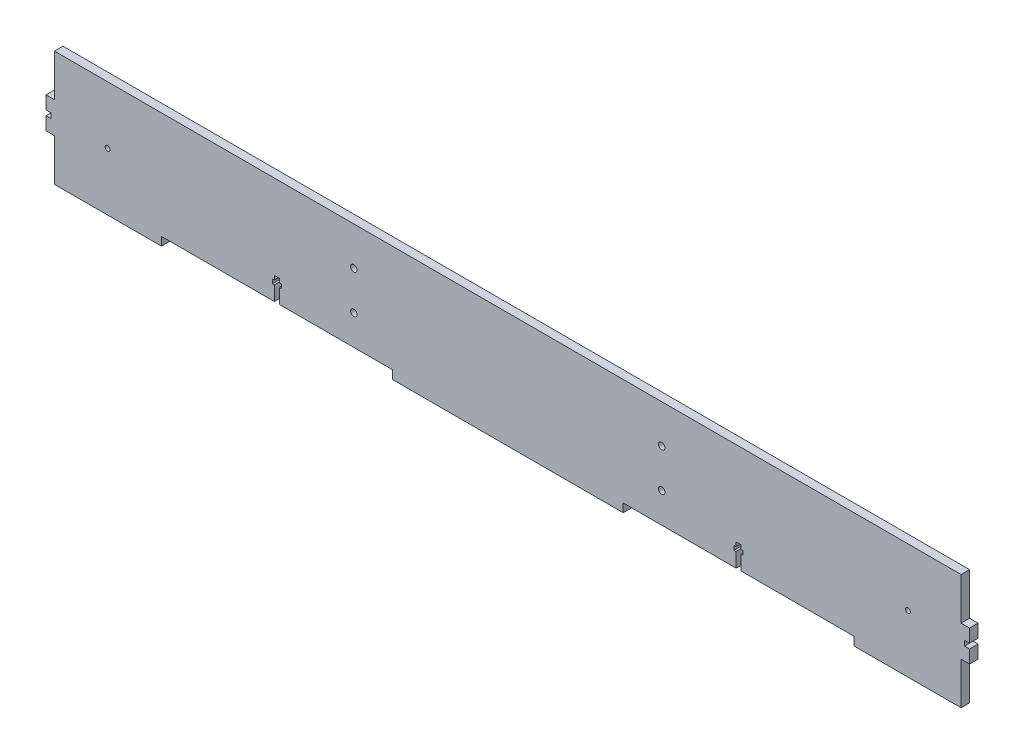
SolidWorks part; units mm, degrees
ref_plane "Front Plane" through (0, 0, 0) normal (0, 0, 1) x (1, 0, 0)
ref_plane "Top Plane" through (0, 0, 0) normal (0, 1, 0) x (1, 0, 0)
ref_plane "Right Plane" through (0, 0, 0) normal (1, 0, 0) x (0, 0, -1)
sketch "Sketch1" plane through (0, 0, 0) normal (0, 0, 1) x (1, 0, 0)
  line L0 (308.5, 78) -> (308.5, 50.625)
  line L1 (308.5, 50.625) -> (303, 50.625)
  line L2 (303, 50.625) -> (303, 42.125)
  line L3 (303, 42.125) -> (306.25, 42.125)
  line L4 (306.25, 42.125) -> (306.25, 40.5)
  line L5 (306.25, 40.5) -> (306.25, 38.875)
  line L6 (306.25, 38.875) -> (303, 38.875)
  line L7 (303, 38.875) -> (303, 30.375)
  line L8 (303, 30.375) -> (308.5, 30.375)
  line L9 (308.5, 30.375) -> (308.5, 3)
  line L10 (308.5, 3) -> (378, 3)
  line L11 (378, 3) -> (378, 8.5)
  line L12 (378, 8.5) -> (451.375, 8.5)
  line L13 (451.375, 8.5) -> (451.375, 17.95)
  line L14 (451.375, 17.95) -> (450.125, 17.95)
  line L15 (450.125, 17.95) -> (450.125, 20.6)
  line L16 (450.125, 20.6) -> (451.375, 20.6)
  line L17 (451.375, 20.6) -> (451.375, 23.25)
  line L18 (451.375, 23.25) -> (454.625, 23.25)
  line L19 (454.625, 23.25) -> (454.625, 20.6)
  line L20 (454.625, 20.6) -> (455.875, 20.6)
  line L21 (455.875, 20.6) -> (455.875, 17.95)
  line L22 (455.875, 17.95) -> (454.625, 17.95)
  line L23 (454.625, 17.95) -> (454.625, 8.5)
  line L24 (454.625, 8.5) -> (528, 8.5)
  line L25 (528, 8.5) -> (528, 3)
  line L26 (528, 3) -> (678, 3)
  line L27 (678, 3) -> (678, 8.5)
  line L28 (678, 8.5) -> (751.375, 8.5)
  line L29 (751.375, 8.5) -> (751.375, 17.95)
  line L30 (751.375, 17.95) -> (750.125, 17.95)
  line L31 (750.125, 17.95) -> (750.125, 20.6)
  line L32 (750.125, 20.6) -> (751.375, 20.6)
  line L33 (751.375, 20.6) -> (751.375, 23.25)
  line L34 (751.375, 23.25) -> (754.625, 23.25)
  line L35 (754.625, 23.25) -> (754.625, 20.6)
  line L36 (754.625, 20.6) -> (755.875, 20.6)
  line L37 (755.875, 20.6) -> (755.875, 17.95)
  line L38 (755.875, 17.95) -> (754.625, 17.95)
  line L39 (754.625, 17.95) -> (754.625, 8.5)
  line L40 (754.625, 8.5) -> (828, 8.5)
  line L41 (828, 8.5) -> (828, 3)
  line L42 (828, 3) -> (897.5, 3)
  line L43 (897.5, 3) -> (897.5, 30.375)
  line L44 (897.5, 30.375) -> (903, 30.375)
  line L45 (903, 30.375) -> (903, 38.875)
  line L46 (903, 38.875) -> (899.75, 38.875)
  line L47 (899.75, 38.875) -> (899.75, 40.5)
  line L48 (899.75, 40.5) -> (899.75, 42.125)
  line L49 (899.75, 42.125) -> (903, 42.125)
  line L50 (903, 42.125) -> (903, 50.625)
  line L51 (903, 50.625) -> (897.5, 50.625)
  line L52 (897.5, 50.625) -> (897.5, 78)
  line L53 (897.5, 78) -> (308.5, 78)
extrude "Boss-Extrude1" add sketch "Sketch1" along normal blind 5.5
sketch "Sketch2" plane through (0, 0, 5.5) normal (0, 0, 1) x (1, 0, 0)
  line L0 (897.5, 78) -> (308.5, 78) construction
  line L1 (503, 53) -> (703, 53)
  line L2 (503, 53) -> (503, 28)
  line L3 (503, 28) -> (703, 28)
  line L4 (703, 53) -> (703, 28)
  circle A0 centre (503, 53) radius 2.1
  circle A1 centre (503, 28) radius 2.1
  circle A2 centre (703, 28) radius 2.1
  circle A3 centre (703, 53) radius 2.1
  point P4 (603, 53)
  point P7 (603, 78)
  dimension "D4" = 4.2
  dimension "D1" = 25
  dimension "D2" = 200
  dimension "D3" = 25
extrude "Cut-Extrude1" cut sketch "Sketch2" against normal through all contours A0 | A1 | A2 | A3
sketch "Sketch3" plane through (0, 0, 5.5) normal (0, 0, 1) x (1, 0, 0)
  line L0 (306.25, 42.125) -> (306.25, 38.875) construction
  line L1 (303, 50.625) -> (303, 42.125) construction
  line L2 (903, 42.125) -> (903, 50.625) construction
  circle A0 centre (343, 40.5) radius 1.6
  circle A1 centre (863, 40.5) radius 1.6
  point P4 (0, 0)
  point P7 (306.25, 40.5)
  dimension "D1" = 3.2
  dimension "D2" = 40
  dimension "D3" = 40
extrude "Cut-Extrude2" cut sketch "Sketch3" against normal through all
